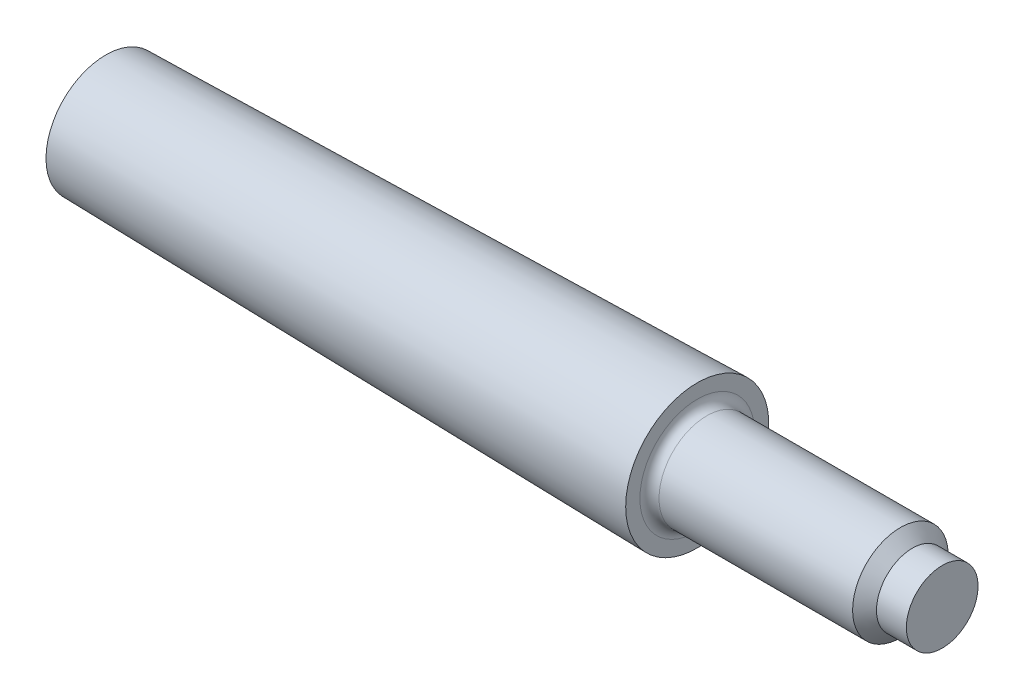
SolidWorks part; units mm, degrees
ref_plane "Front Plane" through (0, 0, 0) normal (0, 0, 1) x (1, 0, 0)
ref_plane "Top Plane" through (0, 0, 0) normal (0, 1, 0) x (1, 0, 0)
ref_plane "Right Plane" through (0, 0, 0) normal (1, 0, 0) x (0, 0, -1)
sketch "BodySke" plane through (0, 0, 0) normal (0, 0, 1) x (1, 0, 0)
  line L0 (0, 0) -> (0, 5) construction
  line L1 (-250, 0) -> (0, 0) construction
  line L2 (0, 5) -> (-250, 0) construction
  line L3 (-99, 0) -> (-99, 10)
  line L4 (-99, 10) -> (0, 11.98)
  line L5 (0, 11.98) -> (0, 8)
  line L6 (0, 8) -> (34, 8)
  line L7 (34, 8) -> (36, 6)
  line L8 (36, 6) -> (41, 6)
  line L9 (41, 6) -> (41, 0)
  line L10 (41, 0) -> (-99, 0)
  line L11 (6, 0) -> (6, 18.5012) construction
  line L12 (39, 0) -> (39, -10.4109) construction
  line L13 (41, 0) -> (76.1668, 0) construction
  point P16 (41, 6.8985)
  dimension "D1" = 5
  dimension "D2" = 250
  dimension "Advance" = 2
  dimension "Thread_minor" = 13.797
revolve "BaseBody" add sketch "BodySke" angle 360 about L1
cosmetic thread "ThreadCosmetic" [suppressed]
fillet "Fillet1" radius 1.6 1 edges at (0, 0, 8)
sketch "ThdSchSke" plane through (0, 0, 0) normal (0, 0, 1) x (1, 0, 0)
  line L0 (0, 0) -> (55.9324, 0) construction
  line L2 (32, 9.2719) -> (32, 8)
  line L3 (32, 9.2719) -> (33.2719, 9.2719)
  line L4 (33.2719, 9.2719) -> (33.2719, 8)
  line L5 (33.2719, 8) -> (32.636, 6.8985)
  line L6 (32.636, 6.8985) -> (32, 8)
  line L7 (0, 8) -> (34, 8) construction
  line L8 (34, 8) -> (34, -8) construction
  dimension "D1" = 2
revolve "ThreadSchematic" [suppressed] cut sketch "ThdSchSke" angle 360 about L0
pattern_linear "ThdSchPat" [suppressed] of bodies 114
equation "\"D1@ThdSchSke\" = \"Advance@BodySke\""
equation "\"Tooth_Num@ThdSchPat\" =  int(  ( \"Thread_length@BodySke\" - \"Dog_length@BodySke\" )  / \"Advance@BodySke\" ) "
equation "\"Advance@ThdSchPat\" = \"Advance@BodySke\""
equation "\"Thread_minor@ThreadCosmetic\" = \"Thread_minor@BodySke\""
equation "\"D1@ThreadCosmetic\" = \"Thread_length@BodySke\" - \"Dog_length@BodySke\""
